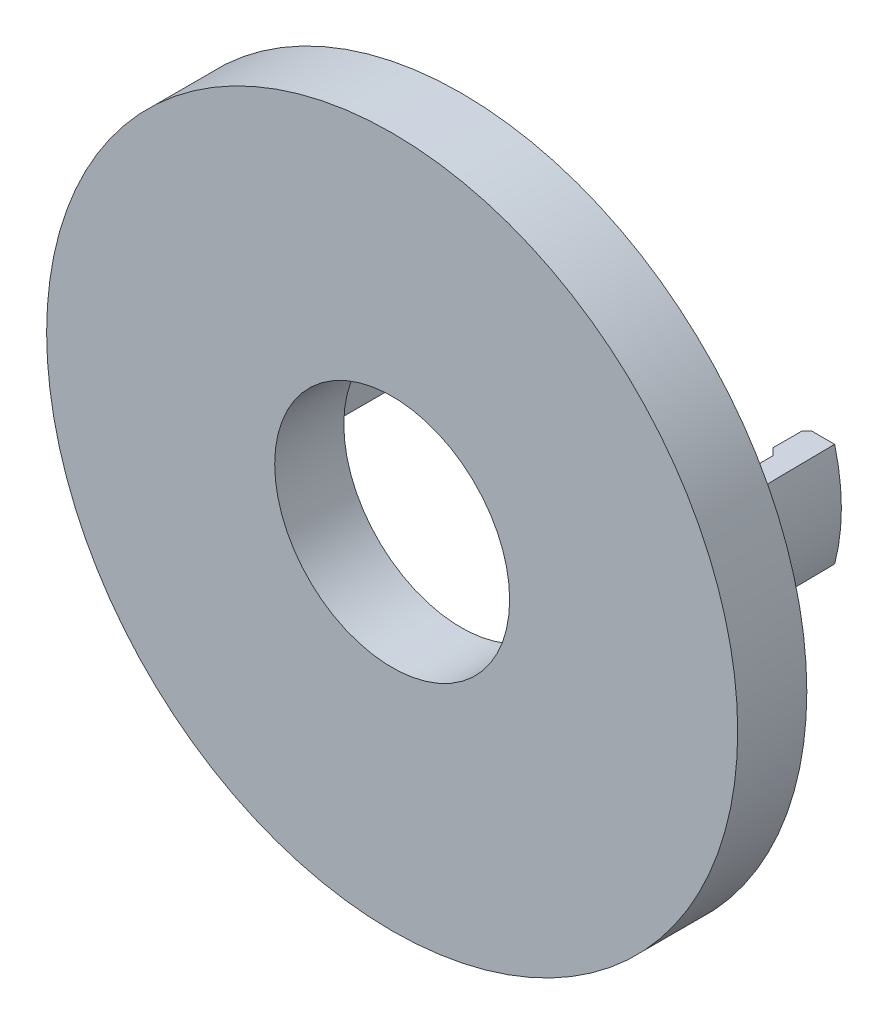
SolidWorks part; units mm, degrees
ref_plane "Front" through (0, 0, 0) normal (0, 0, 1) x (1, 0, 0)
ref_plane "Top" through (0, 0, 0) normal (0, 1, 0) x (1, 0, 0)
ref_plane "Right" through (0, 0, 0) normal (1, 0, 0) x (0, 0, -1)
sketch "Guard base" plane through (0, 0, 0) normal (0, 0, 1) x (1, 0, 0)
  circle A0 centre (0, 0) radius 25
  dimension "D1" = 50
extrude "Guard" add sketch "Guard base" along normal blind 5
sketch "Inner axle hole base" plane through (0, 0, 5) normal (0, 0, 1) x (1, 0, 0)
  circle A0 centre (0, 0) radius 8.5
  dimension "D1" = 17
extrude "Inner axle hole" cut sketch "Inner axle hole base" against normal through all
sketch "Coupling tooth base" plane through (0, 0, 0) normal (0, 1, 0) x (1, 0, 0)
  line L0 (10, 0) -> (15.5, 0) construction
  line L1 (15.5, 0) -> (15.5, 13)
  line L2 (12.5, 2.5) -> (12.5, 9) construction
  line L3 (15.5, 13) -> (12.5, 13) construction
  line L4 (12.5, 13) -> (11.5, 12) construction
  line L5 (11.5, 10) -> (12.5, 9) construction
  line L6 (14.75, 7.0619) -> (14.75, 18.4381) construction
  line L7 (12.75, 9.8107) -> (12.75, 2.3964)
  line L8 (12.5, 2.5) -> (10, 0) construction
  line L9 (12.75, 9.8107) -> (12.25, 10.3107)
  line L10 (11.5, 12) -> (11.5, 10) construction
  line L11 (12.25, 10.3107) -> (12.25, 12.3964)
  line L12 (15.5, 0) -> (15.5, 12.75) construction
  line L13 (15.5, 0) -> (10.3536, 0)
  line L14 (12.75, 2.3964) -> (10.3536, 0)
  line L15 (12.25, 12.3964) -> (12.6036, 12.75)
  line L16 (12.6036, 12.75) -> (15.5, 12.75)
  line L17 (15.5, 12.75) -> (25, 12.75)
  line L18 (25, 12.75) -> (25, 0)
  line L19 (25, 0) -> (15.5, 0)
  spline S0 degree 2 poles (14.75, 12.75) (14.75, 3.4464) (15.5, 0) knots 0 0 0 1 1 1
  point P24 (8.5, 0)
  dimension "D2" = 1
  dimension "D3" = 4
  dimension "D4" = 13
  dimension "D5" = 4
  dimension "D6" = 0.25
  dimension "D7" = 0.25
  dimension "D8" = 0.25
  dimension "D9" = 0.75
  dimension "D10" = 225
  dimension "D11" = 5.5
  dimension "D12" = 0.25
  dimension "D13" = 135
  dimension "D14" = 0.75
  dimension "D15" = 0.75
  dimension "D16" = 1.5
extrude "Coupling tooth" add sketch "Coupling tooth base" along normal blind 3.75 and the other way blind 3.75 contours L16 L15 L11 L9 L7 L14 | L12 L16 region at (15.1845, 0, -7.6129) region at (13.6318, 0, -5.8006)
ref_axis "Center Z" through (0, 0, 0) along (0, 0, -1)
revolve "Circularity cut" cut sketch "Sketch6<4>" angle 360 about axis through (0, 0, 0) along (0, 0, -1) region at (15.1845, 0, -7.6129) region at (20.25, 0, -6.375)
sketch "Sketch6<4>" plane through (0, 0, 0) normal (0, 1, 0) x (1, 0, 0) same geometry as "Coupling tooth base"
mirror "Coutpling teeth" about plane through (0, 0, 0) normal (1, 0, 0) of "Coupling tooth", "Circularity cut"
equation "\"mate_room\"= 0.25"
equation "\"D6@Coupling tooth base\"=\"mate_room\""
equation "\"D8@Coupling tooth base\"=\"mate_room\""
equation "\"D7@Coupling tooth base\"=\"mate_room\""
equation "\"D9@Coupling tooth base\"=\"removal_room\""
equation "\"D12@Coupling tooth base\"=\"mate_room\""
equation "\"D14@Coupling tooth base\"=\"removal_room\""
equation "\"removal_room\"= 0.75"
equation "\"D1@Inner axle hole base\" = \"small_inner_axle_diameter\""
equation "\"guard_thickness\"=5"
equation "\"spool_inner_diameter_room\"=1"
equation "\"32_92_coupling_tooth_height\"=13"
equation "\"32_92_coupling_tooth_thickness_total\"=4"
equation "\"32_92_coupling_tooth_protrusion\"=1"
equation "\"32_92_coupling_tooth_depth\"=8"
equation "\"32_92_coupling_tooth_base_thickness\"=5.5"
equation "\"D1@Guard\"=\"guard_thickness\""
equation "\"32_92_guard_diameter\"=50"
equation "\"D1@Guard base\"=\"32_92_guard_diameter\""
equation "\"D4@Coupling tooth base\"=\"32_92_coupling_tooth_height\""
equation "\"D3@Coupling tooth base\"=\"32_92_coupling_tooth_thickness_total\""
equation "\"D2@Coupling tooth base\"=\"32_92_coupling_tooth_protrusion\""
equation "\"D11@Coupling tooth base\"=\"32_92_coupling_tooth_base_thickness\""
equation "\"32_92_coupling_tooth_head_height\"=4"
equation "\"D5@Coupling tooth base\"=\"32_92_coupling_tooth_head_height\""
equation "\"32_92_spool_inner_diameter\"=32"
equation "\"32_92_spool_thickness\"=92"
equation "\"small_inner_axle_diameter\"=17"
equation "\"D16@Coupling tooth base\" = ( \"large_inner_axle_diameter\" - \"small_inner_axle_diameter\" ) / 2"
equation "\"large_inner_axle_diameter\"=20"
